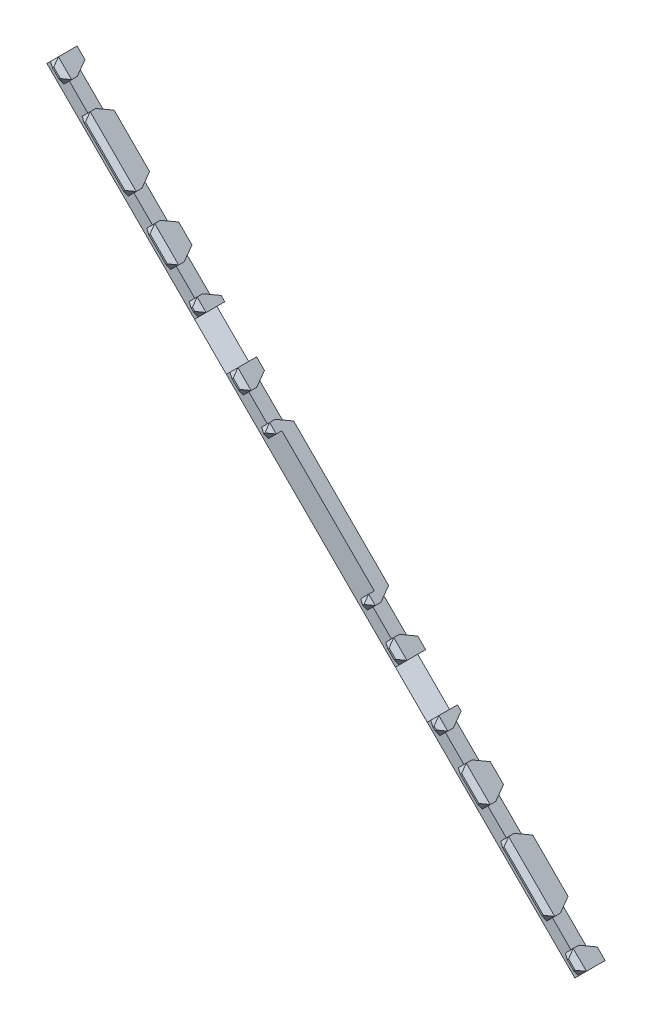
SolidWorks part; units mm, degrees
ref_plane "Ebene vorne" through (0, 0, 0) normal (0, 0, 1) x (1, 0, 0)
ref_plane "Ebene oben" through (0, 0, 0) normal (0, 1, 0) x (1, 0, 0)
ref_plane "Ebene rechts" through (0, 0, 0) normal (1, 0, 0) x (0, 0, -1)
sketch "Skizze1" plane through (0, 0, 0) normal (0, 0, 1) x (1, 0, 0)
  line L0 (0, 0) -> (0, -399.8)
  line L1 (0, 0) -> (-13, 0)
  line L2 (-13, 0) -> (-13, -10)
  line L3 (-13, -10) -> (-7, -10)
  line L4 (-7, -10) -> (-7, -24)
  line L5 (-7, -24) -> (-13, -24)
  line L6 (-13, -24) -> (-13, -58.9)
  line L7 (-13, -58.9) -> (-7, -58.9)
  line L8 (-7, -58.9) -> (-7, -72.9)
  line L9 (-7, -72.9) -> (-13, -72.9)
  line L10 (-13, -72.9) -> (-13, -91)
  line L11 (-13, -91) -> (-7, -91)
  line L12 (-7, -91) -> (-7, -105)
  line L13 (-7, -105) -> (-13, -105)
  line L14 (-13, -105) -> (-13, -111.8)
  line L15 (-13, -111.8) -> (-7, -111.8)
  line L16 (-10, -10) -> (-10, -14) construction
  line L17 (-10, -58.9) -> (-10, -62.9) construction
  line L18 (-10, -105) -> (-10, -101) construction
  line L19 (-7, -111.8) -> (-7, -135.9)
  line L20 (-7, -135.9) -> (-13, -135.9)
  line L21 (-13, -135.9) -> (-13, -145.9)
  line L22 (-13, -145.9) -> (-7, -145.9)
  line L23 (-7, -145.9) -> (-7, -159.9)
  line L24 (-7, -159.9) -> (-13, -159.9)
  line L25 (-13, -159.9) -> (-13, -239.9)
  line L26 (-10, -145.9) -> (-10, -149.9) construction
  line L27 (-13, -199.9) -> (0, -199.9) construction
  line L28 (-10, -253.9) -> (-10, -249.9) construction
  line L29 (-10, -294.8) -> (-10, -298.8) construction
  line L30 (-10, -340.9) -> (-10, -336.9) construction
  line L31 (-10, -389.8) -> (-10, -385.8) construction
  line L32 (-7, -239.9) -> (-13, -239.9)
  line L33 (-7, -253.9) -> (-7, -239.9)
  line L34 (-13, -253.9) -> (-7, -253.9)
  line L35 (-13, -263.9) -> (-13, -253.9)
  line L36 (-7, -263.9) -> (-13, -263.9)
  line L37 (-7, -288) -> (-7, -263.9)
  line L38 (-13, -288) -> (-7, -288)
  line L39 (-13, -294.8) -> (-13, -288)
  line L40 (-7, -294.8) -> (-13, -294.8)
  line L41 (-7, -308.8) -> (-7, -294.8)
  line L42 (-13, -308.8) -> (-7, -308.8)
  line L43 (-13, -326.9) -> (-13, -308.8)
  line L44 (-7, -326.9) -> (-13, -326.9)
  line L45 (-7, -340.9) -> (-7, -326.9)
  line L46 (-13, -340.9) -> (-7, -340.9)
  line L47 (-13, -375.8) -> (-13, -340.9)
  line L48 (-7, -375.8) -> (-13, -375.8)
  line L49 (-7, -389.8) -> (-7, -375.8)
  line L50 (-13, -389.8) -> (-7, -389.8)
  line L51 (-13, -399.8) -> (-13, -389.8)
  line L52 (0, -399.8) -> (-13, -399.8)
  point P3 (-10, -10)
  dimension "D1" = 10
  dimension "D2" = 14
  dimension "D3" = 6
  dimension "D4" = 10
  dimension "D5" = 4
  dimension "D6" = 48.9
  dimension "D7" = 38.1
  dimension "D8" = 10.8
  dimension "D9" = 48.9
  dimension "D10" = 50
extrude "Aufsatz-Linear austragen1" add sketch "Skizze1" along normal blind 7
sketch "Skizze2" plane through (0, 0, 0) normal (0, 0, -1) x (-1, 0, 0)
  line L0 (0, 0) -> (13, 0) construction
  line L1 (13, -10) -> (7, -10)
  line L2 (13, -10) -> (13, 0)
  line L3 (13, 0) -> (7, 0)
  line L4 (7, -10) -> (7, 0)
  line L5 (13, -159.9) -> (13, -239.9) construction
  line L6 (7, -24) -> (13, -24)
  line L7 (7, -24) -> (7, -58.9)
  line L8 (7, -58.9) -> (13, -58.9)
  line L9 (13, -24) -> (13, -58.9)
  line L10 (7, -72.9) -> (13, -72.9)
  line L11 (7, -72.9) -> (7, -91)
  line L12 (7, -91) -> (13, -91)
  line L13 (13, -72.9) -> (13, -91)
  line L14 (7, -105) -> (13, -105)
  line L15 (7, -105) -> (7, -111.8)
  line L16 (7, -111.8) -> (13, -111.8)
  line L17 (13, -105) -> (13, -111.8)
  line L18 (7, -135.9) -> (13, -135.9)
  line L19 (7, -135.9) -> (7, -145.9)
  line L20 (7, -145.9) -> (13, -145.9)
  line L21 (13, -135.9) -> (13, -145.9)
  line L22 (7, -159.9) -> (13, -159.9)
  line L23 (7, -159.9) -> (7, -164.9)
  line L24 (7, -164.9) -> (13, -164.9)
  line L25 (13, -159.9) -> (13, -164.9)
  line L27 (7, -239.9) -> (13, -239.9)
  line L28 (7, -239.9) -> (7, -234.9)
  line L29 (7, -234.9) -> (13, -234.9)
  line L30 (13, -239.9) -> (13, -234.9)
  line L31 (7, -253.9) -> (13, -253.9)
  line L32 (7, -253.9) -> (7, -263.9)
  line L33 (7, -263.9) -> (13, -263.9)
  line L34 (13, -253.9) -> (13, -263.9)
  line L35 (7, -288) -> (13, -288)
  line L36 (7, -288) -> (7, -294.8)
  line L37 (7, -294.8) -> (13, -294.8)
  line L38 (13, -288) -> (13, -294.8)
  line L39 (7, -308.8) -> (13, -308.8)
  line L40 (7, -308.8) -> (7, -326.9)
  line L41 (7, -326.9) -> (13, -326.9)
  line L42 (13, -308.8) -> (13, -326.9)
  line L43 (7, -340.9) -> (13, -340.9)
  line L44 (7, -340.9) -> (7, -375.8)
  line L45 (7, -375.8) -> (13, -375.8)
  line L46 (13, -340.9) -> (13, -375.8)
  line L47 (7, -389.8) -> (13, -389.8)
  line L48 (7, -389.8) -> (7, -399.8)
  line L49 (7, -399.8) -> (13, -399.8)
  line L50 (13, -389.8) -> (13, -399.8)
  dimension "D1" = 5
extrude "Aufsatz-Linear austragen2" add sketch "Skizze2" along normal blind 5.5
chamfer "Fase1" distance 7 angle 30 16 edges at (-10, -389.8, 7) (-10, -375.8, 7) (-10, -340.9, 7) (-10, -326.9, 7) (-10, -308.8, 7) (-10, -294.8, 7) (-10, -253.9, 7) (-10, -239.9, 7) (-10, -159.9, 7) (-10, -145.9, 7) (-10, -105, 7) (-10, -91, 7) (-10, -72.9, 7) (-10, -58.9, 7) (-10, -24, 7) (-10, -10, 7) first distance on face at (-9.4, -389.8, 0.6) first distance on face at (-9.4, -375.8, 0.6) first distance on face at (-9.4, -340.9, 0.6) first distance on face at (-9.4, -326.9, 0.6) first distance on face at (-9.4, -308.8, 0.6) first distance on face at (-9.4, -294.8, 0.6) first distance on face at (-9.4, -253.9, 0.6) first distance on face at (-9.4, -239.9, 0.6) first distance on face at (-9.4, -159.9, 0.6) first distance on face at (-9.4, -145.9, 0.6) first distance on face at (-9.4, -105, 0.6) first distance on face at (-9.4, -91, 0.6) first distance on face at (-9.4, -72.9, 0.6) first distance on face at (-9.4, -58.9, 0.6) first distance on face at (-9.4, -24, 0.6) first distance on face at (-9.4, -10, 0.6)
chamfer "Fase2" distance 7 angle 45 2 edges at (-7, -123.85, 0) (-7, -275.95, 0)
chamfer "Fase3" distance 2.5 angle 45 48 edges at (-10, -10, -5.5) (-10, -389.8, -5.5) (-13, -394.8, -5.5) (-10, -399.8, -5.5) (-7, -394.8, -5.5) (-10, -340.9, -5.5) (-13, -358.35, -5.5) (-10, -375.8, -5.5) (-7, -358.35, -5.5) (-10, -308.8, -5.5) (-13, -317.85, -5.5) (-10, -326.9, -5.5) (-7, -317.85, -5.5) (-10, -288, -5.5) (-13, -291.4, -5.5) (-10, -294.8, -5.5) (-7, -291.4, -5.5) (-10, -253.9, -5.5) (-13, -258.9, -5.5) (-10, -263.9, -5.5) (-7, -258.9, -5.5) (-10, -234.9, -5.5) (-13, -237.4, -5.5) (-10, -239.9, -5.5) (-7, -237.4, -5.5) (-10, -159.9, -5.5) (-13, -162.4, -5.5) (-10, -164.9, -5.5) (-7, -162.4, -5.5) (-10, -135.9, -5.5) (-13, -140.9, -5.5) (-10, -145.9, -5.5) (-7, -140.9, -5.5) (-10, -105, -5.5) (-13, -108.4, -5.5) (-10, -111.8, -5.5) (-7, -108.4, -5.5) (-7, -5, -5.5) (-10, 0, -5.5) (-13, -5, -5.5) (-10, -24, -5.5) (-13, -41.45, -5.5) (-10, -58.9, -5.5) (-7, -41.45, -5.5) (-10, -72.9, -5.5) (-13, -81.95, -5.5) (-10, -91, -5.5) (-7, -81.95, -5.5)
sketch "Skizze4" plane through (0, 0, 7) normal (0, 0, 1) x (1, 0, 0)
  line L0 (-6.5, -28.0415) -> (-6.5, -5.9585) construction
  line L8 (-6.5, -54.8585) -> (-6.5, -76.9415) construction
  line L9 (-6.5, -86.9585) -> (-6.5, -109.0415) construction
  line L10 (-6.5, -141.8585) -> (-6.5, -163.9415) construction
  line L11 (-6.5, -235.8585) -> (-6.5, -257.9415) construction
  line L12 (-6.5, -290.7585) -> (-6.5, -312.8415) construction
  line L13 (-6.5, -322.8585) -> (-6.5, -344.9415) construction
  line L14 (-6.5, -371.7585) -> (-6.5, -393.8415) construction
  line L15 (-7, -5.9585) -> (-7, -28.0415) construction
  line L16 (-7, -28.0415) -> (-13, -28.0415) construction
  line L17 (-13, -5.9585) -> (-7, -5.9585) construction
  line L18 (-13, -54.8585) -> (-7, -54.8585) construction
  line L19 (-7, -76.9415) -> (-13, -76.9415) construction
  line L20 (-13, -86.9585) -> (-7, -86.9585) construction
  line L21 (-7, -109.0415) -> (-13, -109.0415) construction
  line L22 (-13, -141.8585) -> (-7, -141.8585) construction
  line L23 (-7, -163.9415) -> (-13, -163.9415) construction
  line L24 (-13, -235.8585) -> (-7, -235.8585) construction
  line L25 (-7, -257.9415) -> (-13, -257.9415) construction
  line L26 (-13, -290.7585) -> (-7, -290.7585) construction
  line L27 (-7, -312.8415) -> (-13, -312.8415) construction
  line L28 (-13, -322.8585) -> (-7, -322.8585) construction
  line L29 (-7, -344.9415) -> (-13, -344.9415) construction
  line L30 (-13, -371.7585) -> (-7, -371.7585) construction
  line L31 (-7, -393.8415) -> (-13, -393.8415) construction
  text T0 "<b>M3</b>" font "Century Gothic" height in points 22
  text T1 "<b>M5</b>" font "Century Gothic" height in points 22
  text T2 "M3" font "Century Gothic" height in points 22
  text T3 "M3" font "Century Gothic" height in points 22
  text T4 "M3" font "Century Gothic" height in points 22
  text T5 "M3" font "Century Gothic" height in points 22
  text T6 "M5" font "Century Gothic" height in points 22
  text T7 "M3" font "Century Gothic" height in points 22
  dimension "D1" = 0.5
extrude "Schnitt-Linear austragen1" cut sketch "Skizze4" against normal blind 0.5
move or copy body "Körper-Verschieben/Kopieren1" bodies to move or copy 103 copy no rotation origin (-76.2234, -31.5728, 0.75) rotation axis (-0.3827, 0.9239, 0) rotation angle 180
